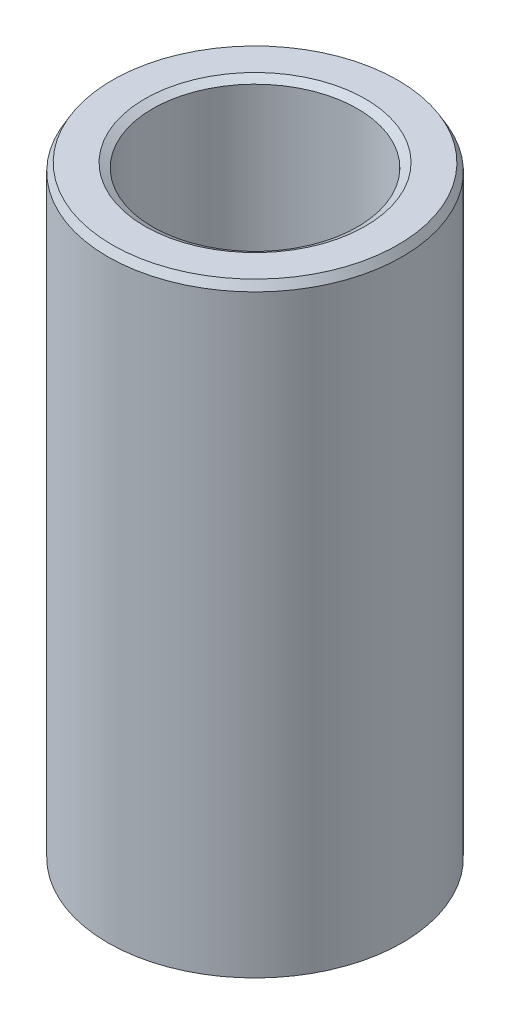
SolidWorks part; units mm, degrees
ref_plane "Front Plane" through (0, 0, 0) normal (0, 0, 1) x (1, 0, 0)
ref_plane "Top Plane" through (0, 0, 0) normal (0, 1, 0) x (1, 0, 0)
ref_plane "Right Plane" through (0, 0, 0) normal (1, 0, 0) x (0, 0, -1)
sketch "Sketch1" plane through (0, 0, 0) normal (0, 1, 0) x (1, 0, 0)
  circle A0 centre (0, 0) radius 40
  dimension "SLEEVE_OD" = 80
extrude "Boss-Extrude1" add sketch "Sketch1" along normal blind 164.7043
sketch "Sketch2" plane through (0, 0, 0) normal (0, 1, 0) x (1, 0, 0)
  circle A0 centre (0, 0) radius 27.8104
  dimension "BORE_D" = 55.6208
extrude "Cut-Extrude1" cut sketch "Sketch2" along normal through all
chamfer "Chamfer1" distance 2.1449 angle 30 4 edges at (0, 164.7043, 27.8104) (0, 0, 27.8104) (0, 0, 40) (0, 164.7043, 40) first distance on face at (0, 164.7043, 27.8104) first distance on face at (0, 0, 27.8104) first distance on face at (0, 164.7043, 40)
